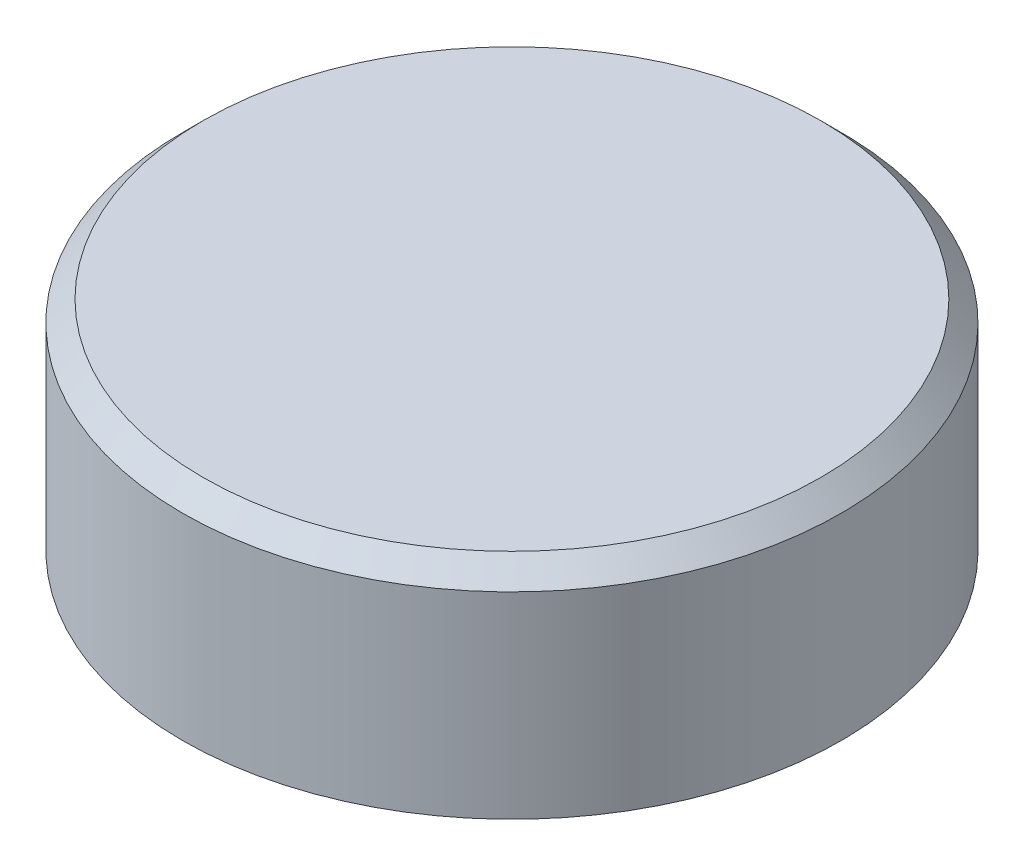
SolidWorks part; units mm, degrees
ref_plane "Front Plane" through (0, 0, 0) normal (0, 0, 1) x (1, 0, 0)
ref_plane "Top Plane" through (0, 0, 0) normal (0, 1, 0) x (1, 0, 0)
ref_plane "Right Plane" through (0, 0, 0) normal (1, 0, 0) x (0, 0, -1)
sketch "Sketch1" plane through (0, 0, 0) normal (0, 1, 0) x (1, 0, 0)
  line L2 (-2.5948, -1.65) -> (2.5948, -1.65)
  arc A0 (2.5948, -1.65) -> (-2.5948, -1.65) centre (0, 0) ccw
  circle A2 centre (0, 0) radius 4.925
  point P5 (0, 0)
  dimension "D1" = 6.15
  dimension "D2" = 9.85
  dimension "D3" = 1.65
extrude "Boss-Extrude1" add sketch "Sketch1" along normal blind 7.5
sketch "Sketch2" plane through (0, 7.5, 0) normal (0, 1, 0) x (1, 0, 0)
  circle A0 centre (0, 0) radius 16
  dimension "D1" = 32
extrude "Boss-Extrude2" add sketch "Sketch2" along normal blind 10.56
sketch "Sketch3" plane through (0, 7.5, 0) normal (0, -1, 0) x (1, 0, 0)
  line L2 (2.5948, 1.65) -> (-2.5948, 1.65)
  line L3 (2.5948, 1.65) -> (-2.5948, 1.65)
  arc A2 (-2.5948, 1.65) -> (2.5948, 1.65) centre (0, 0) ccw
  arc A3 (-2.5948, 1.65) -> (2.5948, 1.65) centre (0, 0) ccw
  dimension "D1" = 0
extrude "Cut-Extrude1" cut sketch "Sketch3" against normal blind 2.5
chamfer "Chamfer1" distance 1 angle 45 1 edges at (0, 18.06, 16)
